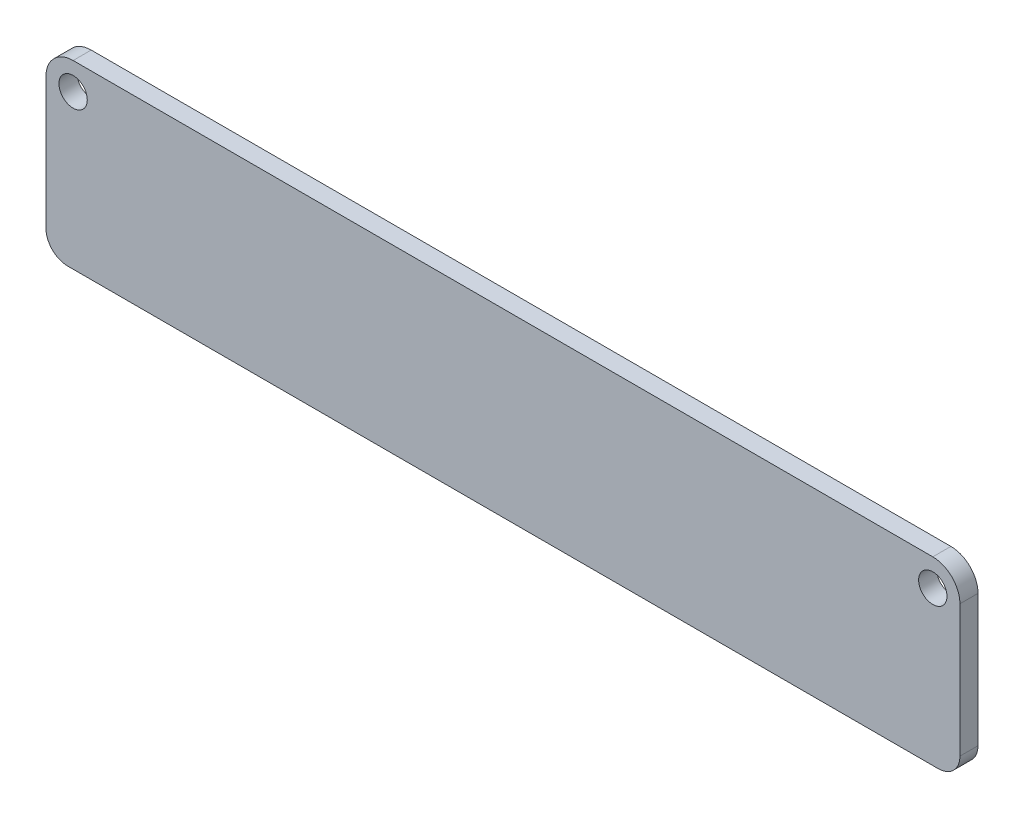
SolidWorks part; units mm, degrees
ref_plane "Front Plane" through (0, 0, 0) normal (0, 0, 1) x (1, 0, 0)
ref_plane "Top Plane" through (0, 0, 0) normal (0, 1, 0) x (1, 0, 0)
ref_plane "Right Plane" through (0, 0, 0) normal (1, 0, 0) x (0, 0, -1)
sketch "Sketch1" plane through (0, 0, 0) normal (0, 0, 1) x (1, 0, 0)
  line L1 (0, 0) -> (-160.528, 0)
  line L2 (0, 0) -> (0, 26.9875)
  line L3 (-4.7625, 31.75) -> (-155.7655, 31.75)
  line L4 (-160.528, 0) -> (-160.528, 26.9875)
  circle A0 centre (-155.7655, 26.9875) radius 2.4892
  circle A1 centre (-155.7655, 26.9875) radius 4.7625
  circle A2 centre (-4.7625, 26.9875) radius 2.4892
  circle A3 centre (-4.7625, 26.9875) radius 4.7625
  dimension "D3" = 4.9784
  dimension "D4" = 9.525
  dimension "D1" = 160.528
  dimension "D2" = 31.75
extrude "Boss-Extrude1" add sketch "Sketch1" along normal blind 3.175 contours A3 L3 A1 L4 L1 L2 | A1 A0 | A3 A2 region at (-80.264, 15.5256, 0) region at (-8.0348, 23.7152, 0) region at (-159.0378, 30.2598, 0)
fillet "Fillet1" radius 3.81 2 edges at (-160.528, 0, 1.5875) (0, 0, 1.5875)
